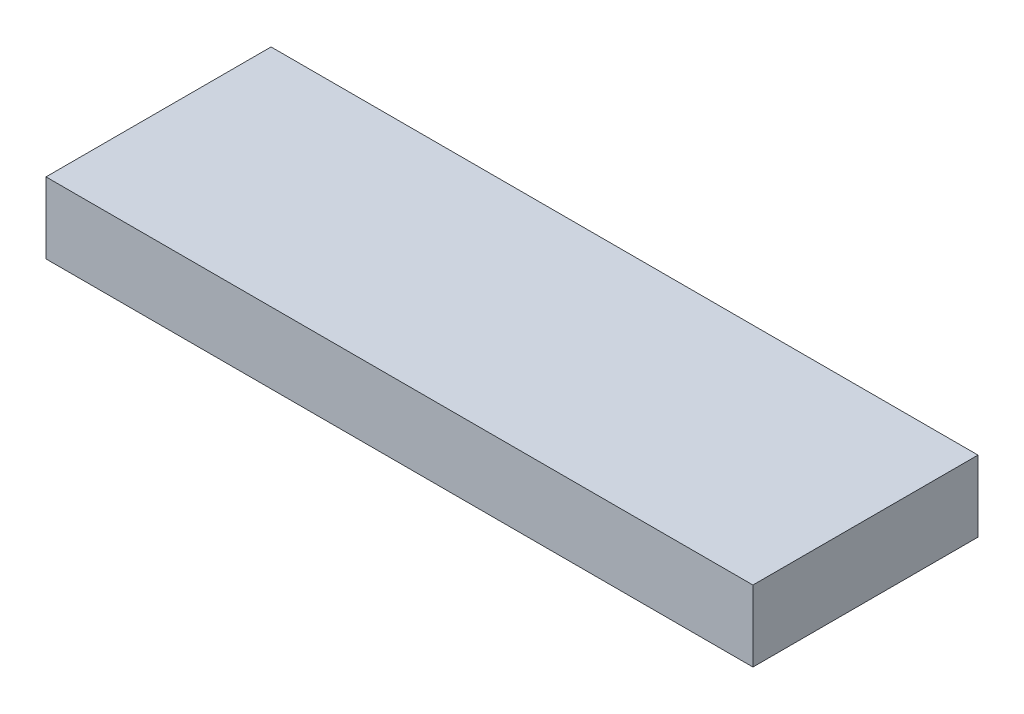
SolidWorks part; units mm, degrees
material "MDF"
ref_plane "Front Plane" through (0, 0, 0) normal (0, 0, 1) x (1, 0, 0)
ref_plane "Top Plane" through (0, 0, 0) normal (0, 1, 0) x (1, 0, 0)
ref_plane "Right Plane" through (0, 0, 0) normal (1, 0, 0) x (0, 0, -1)
sketch "Sketch1" plane through (0, 0, 0) normal (0, 0, 1) x (1, 0, 0)
  line L0 (-94.7388, -19.05) -> (-94.7388, -298.45) construction
  line L1 (-94.7388, -282.575) -> (94.7388, -282.575)
  line L2 (-94.7388, -282.575) -> (-94.7388, -263.525)
  line L3 (-94.7388, -263.525) -> (94.7388, -263.525)
  line L4 (94.7388, -282.575) -> (94.7388, -263.525)
  line L5 (94.7388, -19.05) -> (94.7388, -298.45) construction
  dimension "D1" = 19.05
  dimension "D2" = 3.175
extrude "Boss-Extrude1" add sketch "Sketch1" along normal up to surface (60.325 mm away)
hole_wizard "Hole1" positions "Sketch2" profile "Sketch3" legacy
sketch "Sketch2" plane through (0, 3.175, -25.4) normal (0, 0, -1) x (-1, 0, 0)
  line L0 (218.5638, 0) -> (218.5638, -437.642) construction
  line L4 (104.2638, 0) -> (104.2638, -298.45) construction
  line L13 (120.1388, -463.55) -> (120.1388, -311.15) construction
  line L16 (126.4888, -311.15) -> (113.7888, -311.15) construction
  line L18 (126.4888, -304.8) -> (-126.4888, -304.8) construction
  line L22 (94.7388, -276.225) -> (-94.7388, -276.225) construction
  line L24 (-94.7388, -285.75) -> (-94.7388, -266.7) construction
  line L26 (94.7388, -285.75) -> (94.7388, -266.7) construction
  line L27 (-94.7388, 0) -> (-94.7388, -19.05) construction
  line L29 (94.7388, 0) -> (94.7388, -19.05) construction
  line L31 (94.7388, -9.525) -> (-94.7388, -9.525) construction
  point P15 (218.5638, -31.75)
  point P17 (218.5638, -218.821)
  point P19 (218.5638, -418.592)
  point P28 (104.2638, -19.05)
  point P30 (104.2638, -149.225)
  point P32 (104.2638, -279.4)
  point P69 (120.1388, -330.2)
  point P71 (120.1388, -444.5)
  point P76 (-120.1388, -444.5)
  point P77 (-120.1388, -330.2)
  point P80 (-104.2638, -279.4)
  point P81 (-104.2638, -149.225)
  point P82 (-104.2638, -19.05)
  point P83 (-218.5638, -418.592)
  point P84 (-218.5638, -218.821)
  point P85 (-218.5638, -31.75)
  point P99 (0, -304.8)
  point P101 (107.4388, -304.8)
  point P103 (-107.4388, -304.8)
  point P127 (75.6888, -276.225)
  point P129 (0, -276.225)
  point P131 (-75.6888, -276.225)
  point P152 (75.6888, -9.525)
  point P154 (0, -9.525)
  point P156 (-75.6888, -9.525)
sketch "Sketch3" plane through (75.6888, -6.35, -25.4) normal (1, 0, 0) x (0, 1, 0)
  line L0 (0, 0) -> (0, 39.0539)
  line L1 (0, 39.0539) -> (1.5875, 38.1)
  line L2 (1.5875, 38.1) -> (1.5875, 4.0177)
  line L3 (1.5875, 4.0177) -> (5.08, 0)
  line L4 (5.08, 0) -> (0, 0)
  line L5 (0, -14.3089) -> (0, 102.4216) construction
  line L6 (0, 39.0539) -> (-1.5875, 38.1) construction
  line L7 (-1.5875, 4.0177) -> (-5.08, 0) construction
  dimension "Diameter" = 3.175
  dimension "Depth" = 38.1
  dimension "C-Sink Diameter" = 10.16
  dimension "C-Sink Angle" = 82
  dimension "Drill Angle" = 118
